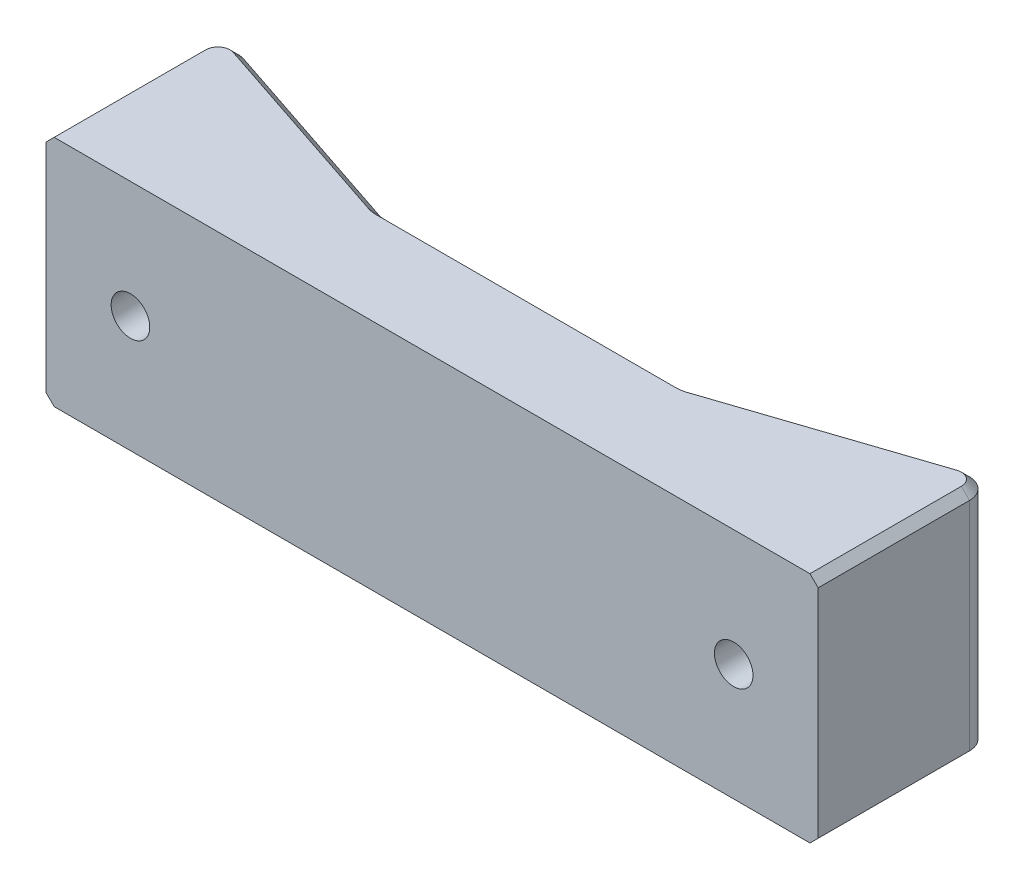
SolidWorks part; units mm, degrees
material "6061-T6 (SS)"
ref_plane "Front Plane" through (0, 0, 0) normal (0, 0, 1) x (1, 0, 0)
ref_plane "Top Plane" through (0, 0, 0) normal (0, 1, 0) x (1, 0, 0)
ref_plane "Right Plane" through (0, 0, 0) normal (1, 0, 0) x (0, 0, -1)
ref_axis "X AXIS" through (-88.99, 0, 0) along (1, 0, 0)
ref_axis "Y AXIS" through (0, -55, 0) along (0, 1, 0)
ref_axis "Z AXIS" through (0, 0, 55) along (0, 0, -1)
other "Freeze***"
sketch "Sketch1" plane through (0, 0, 0) normal (0, 1, 0) x (1, 0, 0)
  line L0 (-48, 0) -> (48, 0)
  line L1 (48, 0) -> (48, 22.35)
  line L2 (48, 22.35) -> (19.05, 12.7)
  line L3 (19.05, 12.7) -> (-19.05, 12.7)
  line L4 (0, 0) -> (0, 12.7) construction
  line L5 (-48, 22.35) -> (-19.05, 12.7)
  line L6 (-48, 0) -> (-48, 22.35)
  point P10 (38.1, 19.05)
  dimension "D1" = 96
  dimension "D2" = 12.7
  dimension "D3" = 38.1
  dimension "D4" = 6.35
  dimension "D5" = 38.1
extrude "Boss-Extrude1" add sketch "Sketch1" along normal mid plane 29
ref_plane "Plane1" through (0, 0, -25.4) normal (0, 0, 1) x (1, 0, 0)
hole_wizard "CSK for M4 Flat Head Machine Screw1" positions "Sketch4" profile "Sketch5" countersink size "M4" standard "ANSI Metric" end condition through all
sketch "Sketch4" plane through (0, 0, -25.4) normal (0, 0, 1) x (1, 0, 0)
  line L0 (-37.5, 0) -> (37.5, 0)
  point P0 (-37.5, 0)
  point P4 (37.5, 0)
  dimension "D1" = 75
sketch "Sketch5" plane through (-37.5, 0, -25.4) normal (1, 0, 0) x (0, 1, 0)
  line L0 (0, 0) -> (0, 25.4)
  line L1 (0, 25.4) -> (2.4, 25.4)
  line L2 (2.4, 25.4) -> (2.4, 15)
  line L3 (2.4, 15) -> (4.7, 12.7)
  line L4 (4.7, 12.7) -> (4.7, 0)
  line L6 (4.7, 0) -> (0, 0)
  line L7 (-2.4, 15) -> (-4.7, 12.7) construction
  line L11 (0, -6.35) -> (0, 107.95) construction
  dimension "Thru Hole Dia." = 4.8
  dimension "Thru Hole Depth" = 25.4
  dimension "C'Sink Dia." = 9.4
  dimension "C'Sink Angle" = 90
  dimension "Head Clearance" = 12.7
fillet "Fillet1" radius 2.54 4 edges at (-48, 0, -22.35) (-19.05, 0, -12.7) (19.05, 0, -12.7) (48, 0, -22.35)
chamfer "Chamfer1" distance 1.016 angle 45 18 edges at (48, -14.5, -9.413) (-48, -14.5, -9.413) (46.9452, -14.5, -20.8865) (-46.9452, -14.5, -20.8865) (32.0489, -14.5, -17.033) (-32.0489, -14.5, -17.033) (19.0447, -14.5, -12.7328) (-19.0447, -14.5, -12.7328) (0, -14.5, -12.7) (48, 14.5, -9.413) (-48, 14.5, -9.413) (46.9452, 14.5, -20.8865) (-46.9452, 14.5, -20.8865) (32.0489, 14.5, -17.033) (-32.0489, 14.5, -17.033) (19.0447, 14.5, -12.7328) (-19.0447, 14.5, -12.7328) (0, 14.5, -12.7)
